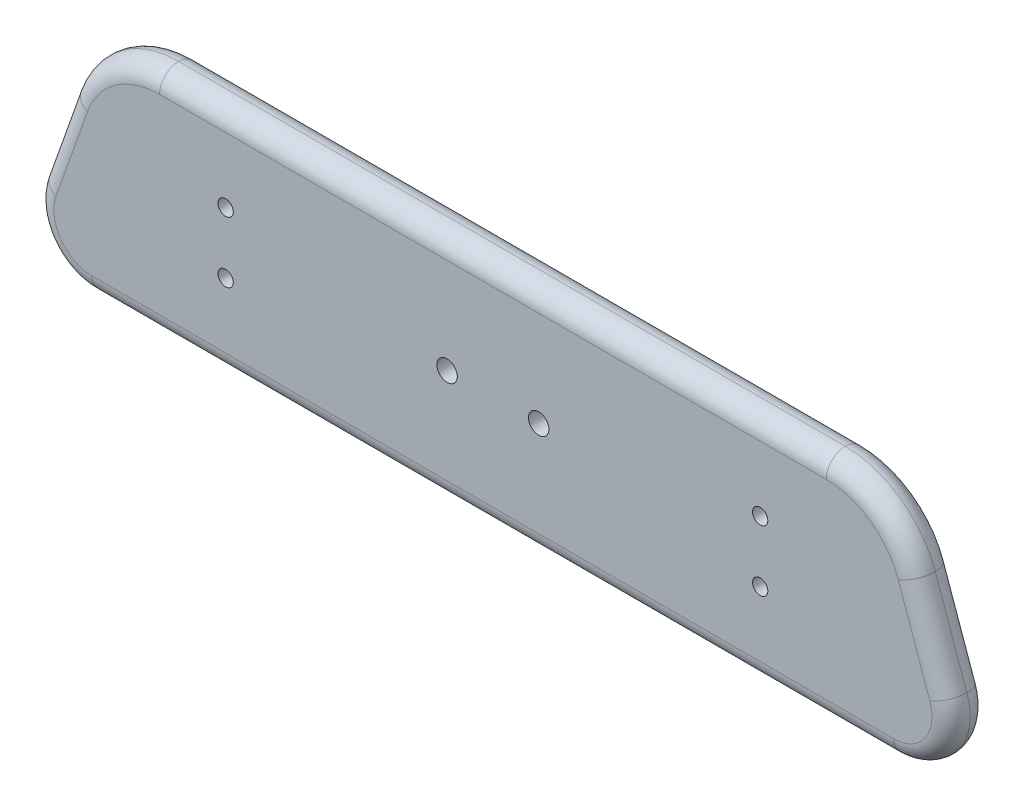
SolidWorks part; units mm, degrees
material "Oak"
ref_plane "Front" through (0, 0, 0) normal (0, 0, 1) x (1, 0, 0)
ref_plane "Top" through (0, 0, 0) normal (0, 1, 0) x (1, 0, 0)
ref_plane "Right" through (0, 0, 0) normal (1, 0, 0) x (0, 0, -1)
sketch "Sketch1" plane through (0, 0, 0) normal (0, 0, 1) x (1, 0, 0)
  line L0 (0, 0) -> (-105, 0)
  line L1 (-119.1396, 20.0071) -> (-110.8752, 43.3452)
  line L2 (-87.3091, 60) -> (87.3091, 60)
  line L3 (110.8752, 43.3452) -> (119.1396, 20.0071)
  line L4 (105, 0) -> (0, 0)
  arc A0 (-105, 0) -> (-119.1396, 20.0071) centre (-105, 15) cw
  arc A1 (-110.8752, 43.3452) -> (-87.3091, 60) centre (-87.3091, 35) cw
  arc A2 (87.3091, 60) -> (110.8752, 43.3452) centre (87.3091, 35) cw
  arc A3 (119.1396, 20.0071) -> (105, 0) centre (105, 15) cw
  point P14 (0, 60)
  dimension "D5" = 25
  dimension "D6" = 15
  dimension "D1" = 60
  dimension "D2" = 105
  dimension "D3" = 210
  dimension "D4" = 70.5
extrude "Boss-Extrude1" add sketch "Sketch1" along normal blind 10
sketch "Sketch2" plane through (0, 0, 10) normal (0, 0, 1) x (1, 0, 0)
  line L0 (-105, 0) -> (105, 0) construction
  line L1 (0, 0) -> (0, 60) construction
  line L2 (87.3091, 60) -> (-87.3091, 60) construction
  circle A0 centre (-70, 22) radius 2
  circle A1 centre (-70, 38) radius 2
  circle A2 centre (70, 22) radius 2
  circle A3 centre (70, 38) radius 2
  dimension "D4" = 4
  dimension "D1" = 22
  dimension "D2" = 38
  dimension "D3" = 70
extrude "Cut-Extrude1" cut sketch "Sketch2" against normal blind 8
fillet "Fillet1" radius 5 16 edges at (-117.2496, 6.3428, 0) (-115.0074, 31.6761, 0) (-101.7378, 55.416, 0) (0, 60, 0) (101.7378, 55.416, 0) (115.0074, 31.6761, 0) (117.2496, 6.3428, 0) (-117.2496, 6.3428, 10) (-115.0074, 31.6761, 10) (-101.7378, 55.416, 10) (0, 60, 10) (101.7378, 55.416, 10) (115.0074, 31.6761, 10) (117.2496, 6.3428, 10) (0, 0, 0) (0, 0, 10)
sketch "Sketch3" plane through (0, 0, 0) normal (0, 0, -1) x (-1, 0, 0)
  line L0 (0, 0) -> (0, 60) construction
  line L2 (23, 10) -> (-23, 10)
  line L3 (-23, 10) -> (-23, 50)
  line L4 (-23, 50) -> (23, 50)
  line L5 (23, 50) -> (23, 10)
  dimension "D1" = 46
  dimension "D2" = 40
  dimension "D3" = 10
  dimension "D4" = 23
extrude "Cut-Extrude2" cut sketch "Sketch3" against normal blind 4
sketch "Sketch4" plane through (0, 0, 4) normal (0, 0, -1) x (-1, 0, 0)
  line L0 (0, 0) -> (0, 60) construction
  line L1 (87.3091, 60) -> (-87.3091, 60) construction
  line L2 (-105, 0) -> (105, 0) construction
  circle A0 centre (-12, 30) radius 2.6722
  circle A1 centre (12, 30) radius 2.6722
  dimension "D1" = 12
  dimension "D2" = 24
  dimension "D3" = 30
extrude "Cut-Extrude3" cut sketch "Sketch4" against normal through all
